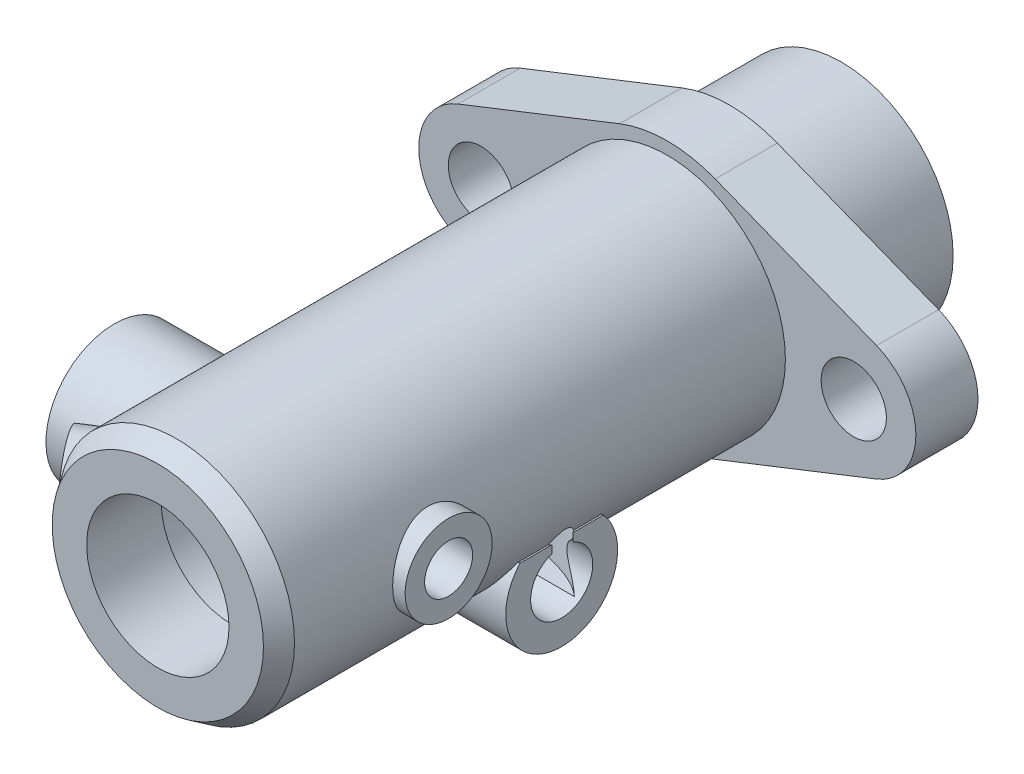
SolidWorks part; units mm, degrees
ref_plane "Front Plane" through (0, 0, 0) normal (0, 0, 1) x (1, 0, 0)
ref_plane "Top Plane" through (0, 0, 0) normal (0, 1, 0) x (1, 0, 0)
ref_plane "Right Plane" through (0, 0, 0) normal (1, 0, 0) x (0, 0, -1)
sketch "Sketch1" plane through (0, 0, 0) normal (0, 0, 1) x (1, 0, 0)
  line L0 (-33.6667, 9.3035) -> (-7.7, 19.5374)
  line L1 (-33.6667, -9.3035) -> (-7.7, -19.5374)
  line L2 (0, -386.7128) -> (0, 18948.9292) construction
  line L3 (33.6667, -9.3035) -> (7.7, -19.5374)
  line L4 (33.6667, 9.3035) -> (7.7, 19.5374)
  line L5 (-1000, 0) -> (49000, 0) construction
  arc A1 (33.6667, -9.3035) -> (33.6667, 9.3035) centre (30, 0) ccw
  arc A2 (-33.6667, 9.3035) -> (-33.6667, -9.3035) centre (-30, 0) ccw
  arc A3 (-7.7, -19.5374) -> (7.7, -19.5374) centre (0, 0) ccw
  arc A4 (7.7, 19.5374) -> (-7.7, 19.5374) centre (0, 0) ccw
  circle A5 centre (-30, 0) radius 5.25
  circle A6 centre (30, 0) radius 5.25
  dimension "D1" = 20
  dimension "D2" = 20
  dimension "D3" = 21
  dimension "D5" = 10.5
  dimension "D4" = 60
extrude "Boss-Extrude1" add sketch "Sketch1" along normal mid plane 10
sketch "Sketch2" plane through (0, 0, -5) normal (0, 0, -1) x (-1, 0, 0)
  circle A0 centre (0, 0) radius 18
  dimension "D1" = 36
extrude "Boss-Extrude2" add sketch "Sketch2" along normal blind 18 contours A0
ref_plane "Plane1" through (0, 0, 87) normal (0, 0, -1) x (-1, 0, 0)
sketch "Sketch3" plane through (0, 0, 0) normal (0, 1, 0) x (1, 0, 0)
  line L1 (7.7, -5) -> (33.6667, -5) construction
  line L5 (19, -70) -> (19, -84)
  line L7 (23.1, -87) -> (-23.1, -87) construction
  line L8 (11.455, -87) -> (11.455, -75)
  line L9 (11.455, -75) -> (12, -75)
  line L10 (12, -75) -> (12, -70)
  line L11 (12, -70) -> (10, -70)
  line L12 (10, -70) -> (10, -66)
  line L13 (10, -66) -> (13.5, -66)
  line L14 (13.5, -66) -> (13.5, -52)
  line L15 (13.5, -52) -> (10, -52)
  line L16 (10, -52) -> (10, -51)
  line L17 (10, -51) -> (7.5, -51)
  line L18 (7.5, -51) -> (7.5, -44)
  line L19 (7.5, -44) -> (13.5, -44)
  line L20 (13.5, -44) -> (13.5, -31)
  line L21 (13.5, -31) -> (15, -31)
  line L22 (15, -31) -> (15, -5)
  line L23 (15, -5) -> (19, -5)
  line L24 (11.455, -87) -> (17, -87)
  line L25 (19, -84) -> (17, -87)
  line L26 (0, -1000) -> (0, 49000) construction
  line L27 (19, -70) -> (19, -5)
  point P6 (19, -87)
  point P32 (14.2275, -87)
  dimension "D1" = 19
  dimension "D3" = 17
  dimension "D4" = 11.455
  dimension "D5" = 12
  dimension "D6" = 12
  dimension "D7" = 5
  dimension "D8" = 10
  dimension "D9" = 4
  dimension "D10" = 13.5
  dimension "D11" = 14
  dimension "D12" = 10
  dimension "D13" = 1
  dimension "D14" = 7.5
  dimension "D15" = 7
  dimension "D16" = 13.5
  dimension "D17" = 13
  dimension "D18" = 15
  dimension "D19" = 82
  dimension "D22" = 3
revolve "Revolve1" add sketch "Sketch3" angle 360 about L26
sketch "Sketch4" plane through (0, 0, 5) normal (0, 0, 1) x (1, 0, 0)
  circle A0 centre (0, 0) radius 15
  dimension "D1" = 30
extrude "Cut-Extrude1" cut sketch "Sketch4" against normal blind 43
ref_plane "Plane2" through (-29, 0, 0) normal (1, 0, 0) x (0, 0, -1)
sketch "Sketch5" plane through (-29, 0, 0) normal (1, 0, 0) x (0, 0, -1)
  line L0 (-87, 17) -> (-87, -17) construction
  circle A0 centre (-65, 0) radius 11
  dimension "D1" = 22
  dimension "D2" = 22
extrude "Boss-Extrude3" add sketch "Sketch5" along normal up to next contours A0
sketch "Sketch6" plane through (-29, 0, 0) normal (-1, 0, 0) x (0, 0, 1)
  circle A0 centre (65, 0) radius 6.5
  dimension "D1" = 13
extrude "Cut-Extrude2" cut sketch "Sketch6" along normal blind 41 from surface contours A0 starting at plane "Right Plane"
ref_plane "Plane3" through (-51.9231, 0, 34.6154) normal (-0.8321, 0, 0.5547) x (0.5547, 0, 0.8321)
sketch "Sketch8" plane through (-51.9231, 0, 34.6154) normal (-0.8321, 0, 0.5547) x (0.5547, 0, 0.8321)
  circle A0 centre (53.2512, 0) radius 6.1017
  ellipse E0 centre (69.8922, 0) end of major axis (69.8922, -19) minor radius 10.5393 construction
  ellipse E1 centre (37.997, 0) end of major axis (37.997, -11) minor radius 9.1526 construction
  ellipse E2 centre (69.8922, 0) end of major axis (69.8922, -19) minor radius 10.5393 construction
  ellipse E3 centre (37.997, 0) end of major axis (37.997, -11) minor radius 9.1526 construction
extrude "Boss-Extrude4" add sketch "Sketch8" against normal up to surface up to face at (19, 0, 84)
sketch "Sketch9" plane through (-51.9231, 0, 34.6154) normal (-0.8321, 0, 0.5547) x (0.5547, 0, 0.8321)
  circle A0 centre (53.2512, 0) radius 5
  arc A2 (51.7819, -5.9221) -> (59.3529, 0) centre (53.2512, 0) ccw construction
  dimension "D1" = 10
hole_wizard "1/16 Rc Tapped Hole5" positions "Sketch20" profile "Sketch21" size "1/16" standard "AS"
sketch "Sketch20" plane through (-51.9231, 0, 34.6154) normal (-0.8321, 0, 0.5547) x (0.5547, 0, 0.8321)
  point P0 (53.2512, 0)
sketch "Sketch21" plane through (-22.3846, 0, 78.9231) normal (0, 1, 0) x (0.5547, 0, 0.8321)
  line L0 (0, 0) -> (0, 11.94)
  line L1 (3.5, 9.837) -> (0, 11.94)
  line L2 (-3.5, 9.837) -> (0, 11.94) construction
  line L3 (3.5, 9.837) -> (3.5, 7.4)
  line L4 (3.5, 7.4) -> (3.4173, 7.4)
  line L5 (3.4173, 7.4) -> (3.571, 2.4751)
  line L6 (3.571, 2.4751) -> (5, 0)
  line L7 (5, 0) -> (0, 0)
  line L8 (0, -6.35) -> (0, 107.95) construction
  line L9 (-3.571, 2.4751) -> (-5, 0) construction
  line L11 (-3.5, 7.4) -> (-3.4173, 7.4) construction
  line L12 (-3.4173, 7.4) -> (-3.571, 2.4751) construction
  dimension "Tap Drill Dia." = 7
  dimension "Tap Drill Depth" = 11.94
  dimension "Thread Dia." = 7.142
  dimension "Thread Angle" = 3.576
  dimension "Thread Depth" = 7.4
  dimension "C'Sink Dia." = 10
  dimension "C'Sink Angle" = 60
  dimension "Drill Angle" = 118
cosmetic thread "Hole Thread3" parameters "D1"=7.4, "D2"=7.723
sketch "Sketch22" plane through (0, 0, 0) normal (1, 0, 0) x (0, 0, -1)
  line L0 (-1000, 0) -> (49000, 0) construction
  line L1 (-87, 17) -> (-87, -17) construction
  line L2 (-45.7082, -9) -> (-32.2918, -9)
  arc A3 (-45.7082, -9) -> (-32.2918, -9) centre (-39, -15) ccw
  circle A4 centre (-39, -15) radius 5
  dimension "D1" = 10
  dimension "D2" = 18
  dimension "D3" = 48
  dimension "D4" = 15
  dimension "D5" = 6
extrude "Boss-Extrude5" add sketch "Sketch22" along normal mid plane 34 contours L2 A3 A4 region at (0, -9.2343, 39)
ref_plane "Plane4" through (21, 0, 0) normal (1, 0, 0) x (0, 0, -1)
sketch "Sketch23" plane through (21, 0, 0) normal (1, 0, 0) x (0, 0, -1)
  line L0 (-87, 17) -> (-87, -17) construction
  line L1 (-1000, 0) -> (49000, 0) construction
  circle A0 centre (-61.2, 0) radius 7
  dimension "D2" = 14
  dimension "D1" = 25.8
extrude "Boss-Extrude6" add sketch "Sketch23" against normal up to surface (2 mm away) up to face at (-9.2384, -2.0987, 73.4565)
sketch "Sketch24" plane through (21, 0, 0) normal (1, 0, 0) x (0, 0, -1)
  circle A0 centre (-61.2, 0) radius 3.8615
  dimension "D1" = 7.723
extrude "Cut-Extrude4" cut sketch "Sketch24" along normal blind 57 from surface starting at plane "Right Plane"
sketch "Sketch25" plane through (0, 0, 0) normal (0, 1, 0) x (1, 0, 0)
  line L0 (0, -1000) -> (0, 49000) construction
  ellipse E0 centre (0, -38.8848) end of major axis (17.5, -38.8848) minor radius 7.1965
  dimension "D1" = 17.5
extrude "Cut-Extrude8" cut sketch "Sketch25" against normal blind 19
